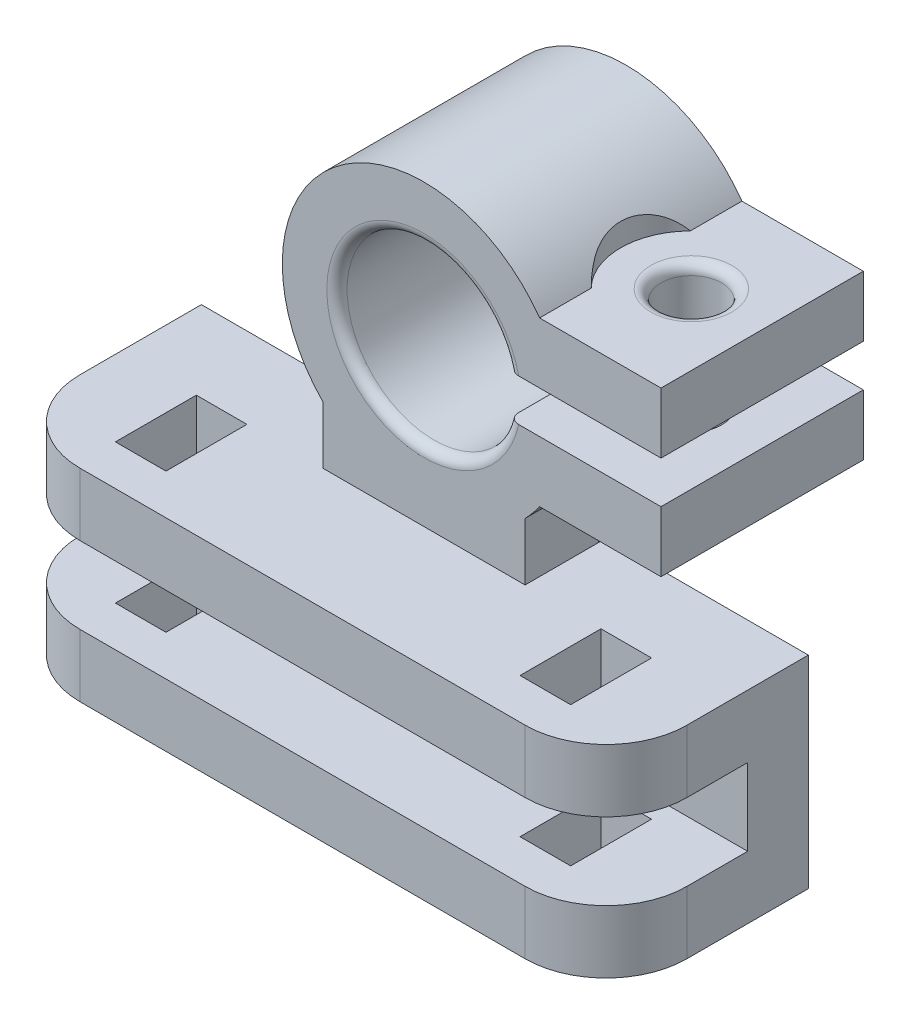
SolidWorks part; units mm, degrees
ref_plane "Plano frontal" through (0, 0, 0) normal (0, 0, 1) x (1, 0, 0)
ref_plane "Plano superior" through (0, 0, 0) normal (0, 1, 0) x (1, 0, 0)
ref_plane "Plano direito" through (0, 0, 0) normal (1, 0, 0) x (0, 0, -1)
sketch "Esboço1" plane through (0, 0, 0) normal (0, 0, 1) x (1, 0, 0)
  line L1 (-15, 5) -> (15, 5)
  line L2 (-15, 5) -> (-15, -5)
  line L3 (-15, -5) -> (15, -5)
  line L4 (15, 5) -> (15, -5)
  line L5 (-15, 5) -> (15, -5) construction
  line L6 (-15, -5) -> (15, 5) construction
  point P0 (0, 0)
  dimension "D1" = 10
  dimension "D2" = 30
extrude "Ressalto-extrusão1" add sketch "Esboço1" along normal blind 10
sketch "Esboço2" plane through (0, 0, 10) normal (0, 0, 1) x (1, 0, 0)
  line L0 (-15, 5) -> (-15, -5) construction
  line L1 (-15, 1.9) -> (15, 1.9)
  line L2 (-15, 1.9) -> (-15, -1.9)
  line L3 (-15, -1.9) -> (15, -1.9)
  line L4 (15, 1.9) -> (15, -1.9)
  line L5 (15, -5) -> (15, 5) construction
  line L6 (-15, 1.9) -> (15, -1.9) construction
  point P8 (0, 0)
  dimension "D1" = 3.8
extrude "Corte-extrusão1" cut sketch "Esboço2" against normal blind 7
fillet "Filete1" radius 4 4 edges at (-15, -3.45, 10) (15, 3.45, 10) (15, -3.45, 10) (-15, 3.45, 10)
sketch "Esboço3" plane through (0, 5, 0) normal (0, 1, 0) x (1, 0, 0)
  line L0 (0, 0) -> (0, -10) construction
  line L5 (11, -10) -> (-11, -10) construction
  line L6 (-10, -6) -> (10, -6) construction
  line L7 (-11.25, -4) -> (-8.75, -8) construction
  line L8 (11.25, -8) -> (8.75, -8)
  line L9 (11.25, -8) -> (11.25, -4)
  line L10 (11.25, -4) -> (8.75, -4)
  line L11 (8.75, -8) -> (8.75, -4)
  line L12 (11.25, -8) -> (8.75, -4) construction
  line L13 (11.25, -4) -> (8.75, -8) construction
  line L14 (-11.25, -8) -> (-8.75, -4) construction
  line L15 (-8.75, -8) -> (-8.75, -4)
  line L16 (-11.25, -4) -> (-8.75, -4)
  line L17 (-11.25, -8) -> (-11.25, -4)
  line L18 (-11.25, -8) -> (-8.75, -8)
  point P12 (0, -6)
  dimension "D1" = 4
  dimension "D2" = 4
  dimension "D3" = 2.5
  dimension "D4" = 20
extrude "Corte-extrusão2" cut sketch "Esboço3" against normal through all
sketch "Esboço4" plane through (0, 0, 0) normal (0, 0, -1) x (-1, 0, 0)
  line L0 (0, 0) -> (0, 1.75) construction
  line L1 (0, 12.75) -> (-7, 12.75) construction
  line L2 (-4.1726, 13.789) -> (-11.7172, 13.789)
  line L3 (-11.7172, 13.789) -> (-11.7172, 16.789)
  line L4 (-11.7172, 16.789) -> (-5.7172, 16.789)
  line L5 (-4.1726, 11.711) -> (-11.7172, 11.711)
  line L6 (-11.7172, 11.711) -> (-11.7172, 8.711)
  line L7 (-11.7172, 8.711) -> (-5.7172, 8.711)
  circle A0 centre (0, 12.75) radius 11 construction
  arc A1 (-4.1726, 11.711) -> (-4.1726, 13.789) centre (0, 12.75) ccw
  arc A2 (-5.7172, 8.711) -> (-5.7172, 16.789) centre (0, 12.75) ccw
  dimension "D1" = 22
  dimension "D3" = 8.6
  dimension "D4" = 14
  dimension "D2" = 1.75
  dimension "D5" = 6
  dimension "D6" = 3
extrude "Ressalto-extrusão2" add sketch "Esboço4" along normal blind 6 and the other way blind 4 separate body
sketch "Esboço5" plane through (0, 0, 4) normal (0, 0, -1) x (-1, 0, 0)
  line L0 (0, 12.75) -> (0, 0) construction
  line L1 (-5, 7.851) -> (5, 7.851)
  line L2 (-5, 7.851) -> (-5, 5)
  line L3 (-5, 5) -> (5, 5)
  line L4 (5, 7.851) -> (5, 5)
  line L6 (-15, 5) -> (15, 5) construction
  arc A0 (-5.7172, 8.711) -> (-5.7172, 16.789) centre (0, 12.75) ccw construction
  arc A1 (-4.1726, 11.711) -> (-4.1726, 13.789) centre (0, 12.75) ccw construction
  point P14 (0, 7.851)
  dimension "D1" = 10
extrude "Ressalto-extrusão3" add sketch "Esboço5" along normal blind 8
combine bodies "Combinar1" operation type add bodies to combine 105 103
chamfer "Chanfro1" distance 4 angle 68 1 edges at (0, 5, 0) first distance on face at (0, 5, -2)
sketch "Esboço7" plane through (0, 16.789, 0) normal (0, 1, 0) x (1, 0, 0)
  line L0 (5.7172, -4) -> (5.7172, 6) construction
  line L1 (11.7172, -4) -> (11.7172, 6) construction
  circle A0 centre (8.2172, 1) radius 1.5
  point P3 (8.2172, 1)
  point P6 (11.7172, 1)
  dimension "D1" = 2.5
  dimension "D2" = 3
extrude "Corte-extrusão3" cut sketch "Esboço7" against normal up to surface (8.078 mm away) up to face at (8.7172, 8.711, -1)
fillet "Filete2" radius 0.5 4 edges at (8.2172, 8.711, -2.5) (-4.3, 12.75, -6) (-4.3, 12.75, 4) (8.2172, 16.789, 0.5)
sketch "Esboço8" plane through (0, 16.789, 0) normal (0, 1, 0) x (1, 0, 0)
  circle A0 centre (8.2172, 1) radius 3.5
  dimension "D1" = 7
extrude "Corte-extrusão4" cut sketch "Esboço8" along normal blind 15
sketch "Esboço9" plane through (0, 8.711, 0) normal (0, -1, 0) x (1, 0, 0)
  circle A0 centre (8.2172, -1) radius 3.5
  dimension "D1" = 7
extrude "Corte-extrusão5" cut sketch "Esboço9" along normal blind 3.7
